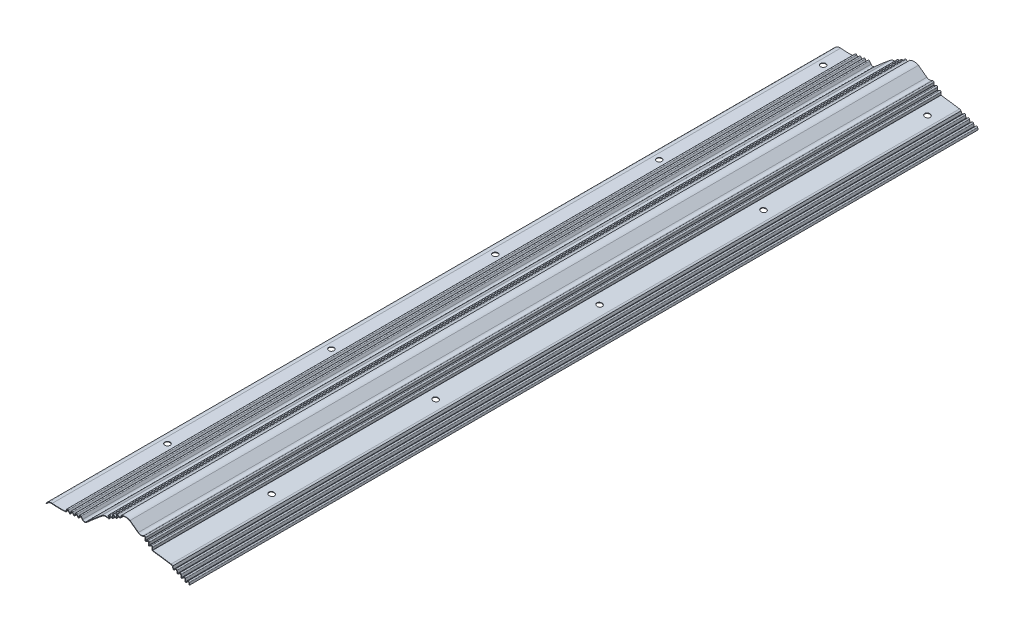
SolidWorks part; units mm, degrees
material "ABS"
ref_plane "Front Plane" through (0, 0, 0) normal (0, 0, 1) x (1, 0, 0)
ref_plane "Top Plane" through (0, 0, 0) normal (0, 1, 0) x (1, 0, 0)
ref_plane "Right Plane" through (0, 0, 0) normal (1, 0, 0) x (0, 0, -1)
sketch "Sketch1" plane through (0, 0, 0) normal (0, 0, 1) x (1, 0, 0)
  line L0 (132.1552, -24.3457) -> (131.5492, -20.6515)
  line L1 (130.3294, -20.1964) -> (126.7023, -23.2139)
  line L2 (124.8385, -22.4334) -> (124.071, -17.7547)
  line L3 (122.8512, -17.2996) -> (119.2255, -20.3159)
  line L4 (117.3602, -19.5364) -> (116.5927, -14.8577)
  line L5 (115.3729, -14.4026) -> (111.7472, -17.4189)
  line L6 (109.8819, -16.6393) -> (109.1144, -11.9607)
  line L7 (107.8946, -11.5055) -> (104.2577, -14.5311)
  line L8 (63.3763, -2.3592) -> (63.7474, 2.3675)
  line L9 (62.6715, 3.1005) -> (58.4307, 1.0365)
  line L10 (56.8053, 2.2387) -> (57.1764, 6.9653)
  line L11 (56.1005, 7.6984) -> (51.8529, 5.631)
  line L12 (50.2374, 6.8363) -> (50.6085, 11.5629)
  line L13 (49.5326, 12.296) -> (47.5397, 11.326)
  line L14 (7.2895, 23.7538) -> (5.1996, 20.1694)
  line L15 (3.3932, 18.9602) -> (-0.6862, 21.3763)
  line L16 (-1.8184, 20.731) -> (-1.8184, 15.9979)
  line L17 (-3.6141, 15.0663) -> (-7.6935, 17.4824)
  line L18 (-8.8257, 16.8371) -> (-8.8257, 12.1063)
  line L19 (-10.6221, 11.1706) -> (-14.7015, 13.5867)
  line L20 (-15.8337, 12.9414) -> (-15.8337, 8.2232)
  line L21 (-65.9213, -18.2913) -> (-68.6357, -14.4708)
  line L22 (-69.9314, -14.5981) -> (-71.863, -18.903)
  line L23 (-73.88, -19.021) -> (-76.626, -15.156)
  line L24 (-77.9216, -15.2833) -> (-79.8524, -19.5864)
  line L25 (-81.8705, -19.7061) -> (-84.6165, -15.8411)
  line L26 (-85.9122, -15.9684) -> (-87.8429, -20.2715)
  line L27 (-89.861, -20.3912) -> (-92.607, -16.5262)
  line L28 (-93.9027, -16.6535) -> (-95.8403, -20.9718)
  line L29 (133.142, -24.1838) -> (132.1552, -24.3457)
  line L30 (-133.142, -25.7205) -> (-132.3004, -26.2607)
  line L31 (133.142, -24.1838) -> (132.536, -20.4896)
  line L32 (129.6899, -19.4276) -> (126.1425, -22.3788)
  line L33 (125.8174, -22.2234) -> (125.0578, -17.5929)
  line L34 (122.2117, -16.5308) -> (118.6649, -19.4815)
  line L35 (118.3391, -19.3264) -> (117.5795, -14.6958)
  line L36 (114.7334, -13.6338) -> (111.1866, -16.5844)
  line L37 (110.8608, -16.4293) -> (110.1012, -11.7988)
  line L38 (107.255, -10.7367) -> (103.6962, -13.6974)
  line L39 (64.3771, -2.3888) -> (64.7443, 2.2892)
  line L40 (62.2338, 3.9997) -> (58.0855, 1.9806)
  line L41 (57.8061, 2.209) -> (58.1733, 6.8871)
  line L42 (55.6629, 8.5975) -> (51.5129, 6.5777)
  line L43 (51.2382, 6.8066) -> (51.6054, 11.4846)
  line L44 (49.095, 13.1951) -> (47.1021, 12.2252)
  line L45 (6.5798, 24.5219) -> (4.1046, 20.2767)
  line L46 (3.8609, 19.8455) -> (-0.1765, 22.2368)
  line L47 (-2.8184, 20.731) -> (-2.8184, 16.1017)
  line L48 (-3.1465, 15.9515) -> (-7.1839, 18.3428)
  line L49 (-9.8257, 16.8371) -> (-9.8257, 12.2078)
  line L50 (-10.1544, 12.0559) -> (-14.1918, 14.4471)
  line L51 (-16.8337, 12.9414) -> (-16.8337, 8.3269)
  line L52 (-65.1061, -17.7121) -> (-67.8205, -13.8916)
  line L53 (-70.8438, -14.1888) -> (-72.7328, -18.3988)
  line L54 (-73.093, -18.4021) -> (-75.8108, -14.5768)
  line L55 (-78.834, -14.874) -> (-80.7227, -19.0833)
  line L56 (-81.0835, -19.0872) -> (-83.8013, -15.2619)
  line L57 (-86.8245, -15.5591) -> (-88.7132, -19.7684)
  line L58 (-89.0741, -19.7723) -> (-91.7918, -15.947)
  line L59 (-94.8151, -16.2442) -> (-96.7102, -20.4678)
  arc A0 (-121.6071, -20.1385) -> (-133.142, -25.7205) centre (-122.8169, -32.3475) ccw
  arc A1 (131.5492, -20.6515) -> (130.3294, -20.1964) centre (130.8091, -20.7729) ccw
  arc A2 (124.8385, -22.4334) -> (126.7023, -23.2139) centre (126.0547, -22.1447) ccw
  arc A3 (124.071, -17.7547) -> (122.8512, -17.2996) centre (123.3309, -17.8762) ccw
  arc A4 (117.3602, -19.5364) -> (119.2255, -20.3159) centre (118.5764, -19.2477) ccw
  arc A5 (116.5927, -14.8577) -> (115.3729, -14.4026) centre (115.8526, -14.9791) ccw
  arc A6 (109.8819, -16.6393) -> (111.7472, -17.4189) centre (111.0981, -16.3506) ccw
  arc A7 (109.1144, -11.9607) -> (107.8946, -11.5055) centre (108.3742, -12.0821) ccw
  arc A8 (102.3957, -13.7736) -> (104.2577, -14.5311) centre (103.6068, -13.464) ccw
  arc A9 (102.3957, -13.7736) -> (100.93, -9.6792) centre (79.8263, -19.5436) ccw
  arc A10 (100.93, -9.6792) -> (98.6738, -8.4536) centre (98.1102, -12.1806) ccw
  arc A11 (98.6738, -8.4536) -> (64.4626, -3.6083) centre (-176.189, -1825.9723) ccw
  arc A12 (63.3763, -2.3592) -> (64.4626, -3.6083) centre (64.6263, -2.369) ccw
  arc A13 (63.7474, 2.3675) -> (62.6715, 3.1005) centre (62.9997, 2.4262) ccw
  arc A14 (56.8053, 2.2387) -> (58.4307, 1.0365) centre (58.0553, 2.2288) ccw
  arc A15 (57.1764, 6.9653) -> (56.1005, 7.6984) centre (56.4287, 7.024) ccw
  arc A16 (50.2374, 6.8363) -> (51.8529, 5.631) centre (51.4874, 6.8264) ccw
  arc A17 (50.6085, 11.5629) -> (49.5326, 12.296) centre (49.8608, 11.6216) ccw
  arc A18 (37.6633, 12.2474) -> (47.5397, 11.326) centre (43.3597, 19.9144) ccw
  arc A19 (37.6633, 12.2474) -> (22.2002, 23.6803) centre (-2424.6999, -3301.9219) ccw
  arc A20 (22.2002, 23.6803) -> (7.2895, 23.7538) centre (14.6679, 8.0898) ccw
  arc A21 (3.3932, 18.9602) -> (5.1996, 20.1694) centre (3.9529, 20.0779) ccw
  arc A22 (-0.6862, 21.3763) -> (-1.8184, 20.731) centre (-1.0684, 20.731) ccw
  arc A23 (-3.6141, 15.0663) -> (-1.8184, 15.9979) centre (-3.0544, 16.184) ccw
  arc A24 (-7.6935, 17.4824) -> (-8.8257, 16.8371) centre (-8.0757, 16.8371) ccw
  arc A25 (-10.6221, 11.1706) -> (-8.8257, 12.1063) centre (-10.0624, 12.2883) ccw
  arc A26 (-14.7015, 13.5867) -> (-15.8337, 12.9414) centre (-15.0837, 12.9414) ccw
  arc A27 (-17.5247, 7.2449) -> (-15.8337, 8.2232) centre (-17.0697, 8.4092) ccw
  arc A28 (-17.5247, 7.2449) -> (-21.1328, 8.1157) centre (-22.5173, -5.5324) ccw
  arc A29 (-21.1328, 8.1157) -> (-29.3192, 5.2985) centre (-22.1751, -2.1585) ccw
  arc A30 (-29.3192, 5.2985) -> (-57.9891, -19.1637) centre (398.8659, -525.571) ccw
  arc A31 (-65.9213, -18.2913) -> (-57.9891, -19.1637) centre (-61.567, -15.1977) ccw
  arc A32 (-68.6357, -14.4708) -> (-69.9314, -14.5981) centre (-69.2471, -14.9052) ccw
  arc A33 (-73.88, -19.021) -> (-71.863, -18.903) centre (-72.9145, -18.2271) ccw
  arc A34 (-76.626, -15.156) -> (-77.9216, -15.2833) centre (-77.2374, -15.5904) ccw
  arc A35 (-81.8705, -19.7061) -> (-79.8524, -19.5864) centre (-80.905, -18.9122) ccw
  arc A36 (-84.6165, -15.8411) -> (-85.9122, -15.9684) centre (-85.2279, -16.2755) ccw
  arc A37 (-89.861, -20.3912) -> (-87.8429, -20.2715) centre (-88.8955, -19.5973) ccw
  arc A38 (-92.607, -16.5262) -> (-93.9027, -16.6535) centre (-93.2184, -16.9606) ccw
  arc A39 (-96.8147, -21.5459) -> (-95.8403, -20.9718) centre (-96.8971, -20.2921) ccw
  arc A40 (-121.7057, -21.1336) -> (-96.8147, -21.5459) centre (-106.7582, 129.7076) ccw
  arc A41 (-121.7057, -21.1336) -> (-132.3004, -26.2607) centre (-122.8169, -32.3475) ccw
  arc A42 (132.536, -20.4896) -> (129.6899, -19.4276) centre (130.8091, -20.7729) ccw
  arc A43 (125.8174, -22.2234) -> (126.1425, -22.3788) centre (126.0547, -22.1447) ccw
  arc A44 (125.0578, -17.5929) -> (122.2117, -16.5308) centre (123.3309, -17.8762) ccw
  arc A45 (118.3391, -19.3264) -> (118.6649, -19.4815) centre (118.5764, -19.2477) ccw
  arc A46 (117.5795, -14.6958) -> (114.7334, -13.6338) centre (115.8526, -14.9791) ccw
  arc A47 (110.8608, -16.4293) -> (111.1866, -16.5844) centre (111.0981, -16.3506) ccw
  arc A48 (110.1012, -11.7988) -> (107.255, -10.7367) centre (108.3742, -12.0821) ccw
  arc A49 (103.3646, -13.5259) -> (103.6962, -13.6974) centre (103.6068, -13.464) ccw
  arc A50 (103.3646, -13.5259) -> (101.7771, -9.1309) centre (79.8263, -19.5436) ccw
  arc A51 (101.7771, -9.1309) -> (98.8233, -7.4648) centre (98.1102, -12.1806) ccw
  arc A52 (98.8233, -7.4648) -> (64.5936, -2.6169) centre (-176.189, -1825.9723) ccw
  arc A53 (64.3771, -2.3888) -> (64.5936, -2.6169) centre (64.6263, -2.369) ccw
  arc A54 (64.7443, 2.2892) -> (62.2338, 3.9997) centre (62.9997, 2.4262) ccw
  arc A55 (57.8061, 2.209) -> (58.0855, 1.9806) centre (58.0553, 2.2288) ccw
  arc A56 (58.1733, 6.8871) -> (55.6629, 8.5975) centre (56.4287, 7.024) ccw
  arc A57 (51.2382, 6.8066) -> (51.5129, 6.5777) centre (51.4874, 6.8264) ccw
  arc A58 (51.6054, 11.4846) -> (49.095, 13.1951) centre (49.8608, 11.6216) ccw
  arc A59 (38.2596, 13.0501) -> (47.1021, 12.2252) centre (43.3597, 19.9144) ccw
  arc A60 (38.2596, 13.0501) -> (22.7195, 24.5398) centre (-2424.6999, -3301.9219) ccw
  arc A61 (22.7195, 24.5398) -> (6.5798, 24.5219) centre (14.6679, 8.0898) ccw
  arc A62 (3.8609, 19.8455) -> (4.1046, 20.2767) centre (3.9529, 20.0779) ccw
  arc A63 (-0.1765, 22.2368) -> (-2.8184, 20.731) centre (-1.0684, 20.731) ccw
  arc A64 (-3.1465, 15.9515) -> (-2.8184, 16.1017) centre (-3.0544, 16.184) ccw
  arc A65 (-7.1839, 18.3428) -> (-9.8257, 16.8371) centre (-8.0757, 16.8371) ccw
  arc A66 (-10.1544, 12.0559) -> (-9.8257, 12.2078) centre (-10.0624, 12.2883) ccw
  arc A67 (-14.1918, 14.4471) -> (-16.8337, 12.9414) centre (-15.0837, 12.9414) ccw
  arc A68 (-17.1607, 8.1763) -> (-16.8337, 8.3269) centre (-17.0697, 8.4092) ccw
  arc A69 (-17.1607, 8.1763) -> (-21.0319, 9.1106) centre (-22.5173, -5.5324) ccw
  arc A70 (-21.0319, 9.1106) -> (-29.9794, 6.0507) centre (-22.1751, -2.1585) ccw
  arc A71 (-29.9794, 6.0507) -> (-58.6589, -18.4212) centre (398.8659, -525.571) ccw
  arc A72 (-65.1061, -17.7121) -> (-58.6589, -18.4212) centre (-61.567, -15.1977) ccw
  arc A73 (-67.8205, -13.8916) -> (-70.8438, -14.1888) centre (-69.2471, -14.9052) ccw
  arc A74 (-73.093, -18.4021) -> (-72.7328, -18.3988) centre (-72.9145, -18.2271) ccw
  arc A75 (-75.8108, -14.5768) -> (-78.834, -14.874) centre (-77.2374, -15.5904) ccw
  arc A76 (-81.0835, -19.0872) -> (-80.7227, -19.0833) centre (-80.905, -18.9122) ccw
  arc A77 (-83.8013, -15.2619) -> (-86.8245, -15.5591) centre (-85.2279, -16.2755) ccw
  arc A78 (-89.0741, -19.7723) -> (-88.7132, -19.7684) centre (-88.8955, -19.5973) ccw
  arc A79 (-91.7918, -15.947) -> (-94.8151, -16.2442) centre (-93.2184, -16.9606) ccw
  arc A80 (-96.8803, -20.5481) -> (-96.7102, -20.4678) centre (-96.8971, -20.2921) ccw
  arc A81 (-121.6071, -20.1385) -> (-96.8803, -20.5481) centre (-106.7582, 129.7076) ccw
  dimension "D1" = 1
extrude "Boss-Extrude2" add sketch "Sketch1" along normal blind 1462
ref_axis "Axis1" through (0, -222.5659, 0) along (0, 1, 0)
sketch "Sketch2" plane through (0, 0, 0) normal (0, 1, 0) x (1, 0, 0)
  circle A0 centre (82.0905, -42.6838) radius 5
  circle A1 centre (-111.1465, -42.6838) radius 5
  dimension "D1" = 10
extrude "Cut-Extrude1" cut sketch "Sketch2" against normal through all both and the other way through all
pattern_linear "LPattern1" count 6 spacing 304 along (0, 0, 1) of "Cut-Extrude1"
